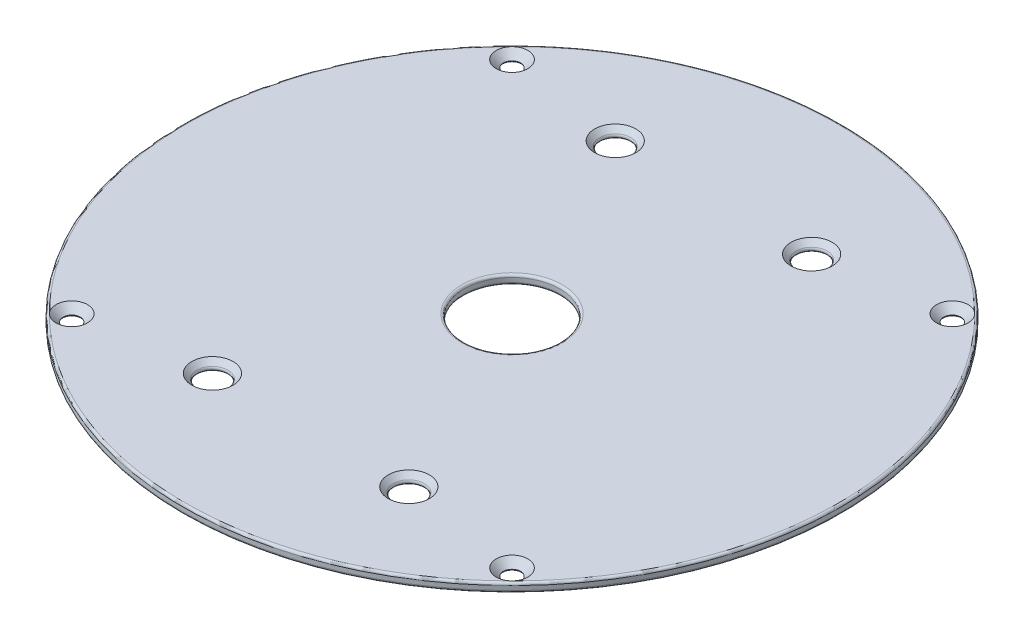
SolidWorks part; units mm, degrees
ref_plane "Front Plane" through (0, 0, 0) normal (0, 0, 1) x (1, 0, 0)
ref_plane "Top Plane" through (0, 0, 0) normal (0, 1, 0) x (1, 0, 0)
ref_plane "Right Plane" through (0, 0, 0) normal (1, 0, 0) x (0, 0, -1)
sketch "Sketch1" plane through (0, 0, 0) normal (0, 1, 0) x (1, 0, 0)
  line L0 (0, 0) -> (-45.9619, 45.9619) construction
  line L1 (20.5, -42.05) -> (-20.5, -42.05) construction
  line L2 (20.5, -42.05) -> (20.5, 42.05) construction
  line L3 (20.5, 42.05) -> (-20.5, 42.05) construction
  line L4 (-20.5, -42.05) -> (-20.5, 42.05) construction
  line L5 (0, 42.05) -> (0, -42.05) construction
  line L6 (20.5, 0) -> (-20.5, 0) construction
  line L7 (0, 0) -> (45.9619, 45.9619) construction
  line L8 (0, 0) -> (45.9619, -45.9619) construction
  line L9 (0, 0) -> (-45.9619, -45.9619) construction
  line L11 (-45.9619, 45.9619) -> (-42.4264, 42.4264) construction
  circle A0 centre (0, 0) radius 69 construction
  circle A1 centre (0, 0) radius 68.8
  circle A2 centre (-20.5, 42.05) radius 2 construction
  circle A3 centre (20.5, 42.05) radius 2 construction
  circle A4 centre (-20.5, -42.05) radius 2
  circle A5 centre (20.5, -42.05) radius 2
  circle A6 centre (-20.5, 42.05) radius 2.3
  circle A7 centre (20.5, 42.05) radius 2.3
  circle A8 centre (20.5, -42.05) radius 2.3
  circle A9 centre (-20.5, -42.05) radius 2.3
  circle A10 centre (0, 0) radius 10
  circle A11 centre (-45.9619, 45.9619) radius 1.5 construction
  circle A13 centre (-45.9619, 45.9619) radius 1.8
  circle A14 centre (45.9619, 45.9619) radius 1.8
  circle A15 centre (45.9619, 45.9619) radius 1.5 construction
  circle A16 centre (45.9619, -45.9619) radius 1.8
  circle A17 centre (45.9619, -45.9619) radius 1.5 construction
  circle A18 centre (-45.9619, -45.9619) radius 1.8
  circle A19 centre (-45.9619, -45.9619) radius 1.5 construction
  point P21 (0, 0)
  point P40 (0, 0)
  dimension "D1" = 138
  dimension "D5" = 4
  dimension "D7" = 20
  dimension "D9" = 3
  dimension "D3" = 84.1
  dimension "D4" = 41
  dimension "D8" = 45
  dimension "D11" = 65
  dimension "D2" = 0.2
  dimension "D6" = 0.3
  dimension "D10" = 0.3
  dimension "D12" = 4
extrude "Boss-Extrude1" add sketch "Sketch1" along normal blind 1.9 contours A1 A10 A9 A8 A7 A6 region at (-66.854, 0, 0)
chamfer "Chamfer1" distance 2 angle 45 4 edges at (-20.5, 1.9, -39.75) (20.5, 1.9, -39.75) (20.5, 1.9, 44.35) (-20.5, 1.9, 44.35)
chamfer "Chamfer3" distance 1.5 angle 45 4 edges at (-45.9619, 1.9, -44.1619) (45.9619, 1.9, 47.7619) (-45.9619, 1.9, 47.7619) (45.9619, 1.9, -44.1619)
fillet "Fillet2" radius 0.5 12 edges at (-20.5, 0, -39.65) (20.5, 0, -39.65) (20.5, 0, 44.45) (-20.5, 0, 44.45) (-45.9619, 0, -44.1619) (45.9619, 0, -44.1619) (45.9619, 0, 47.7619) (-45.9619, 0, 47.7619) (0, 0, 10) (0, 1.9, 10) (0, 0, 68.8) (0, 1.9, 68.8)
